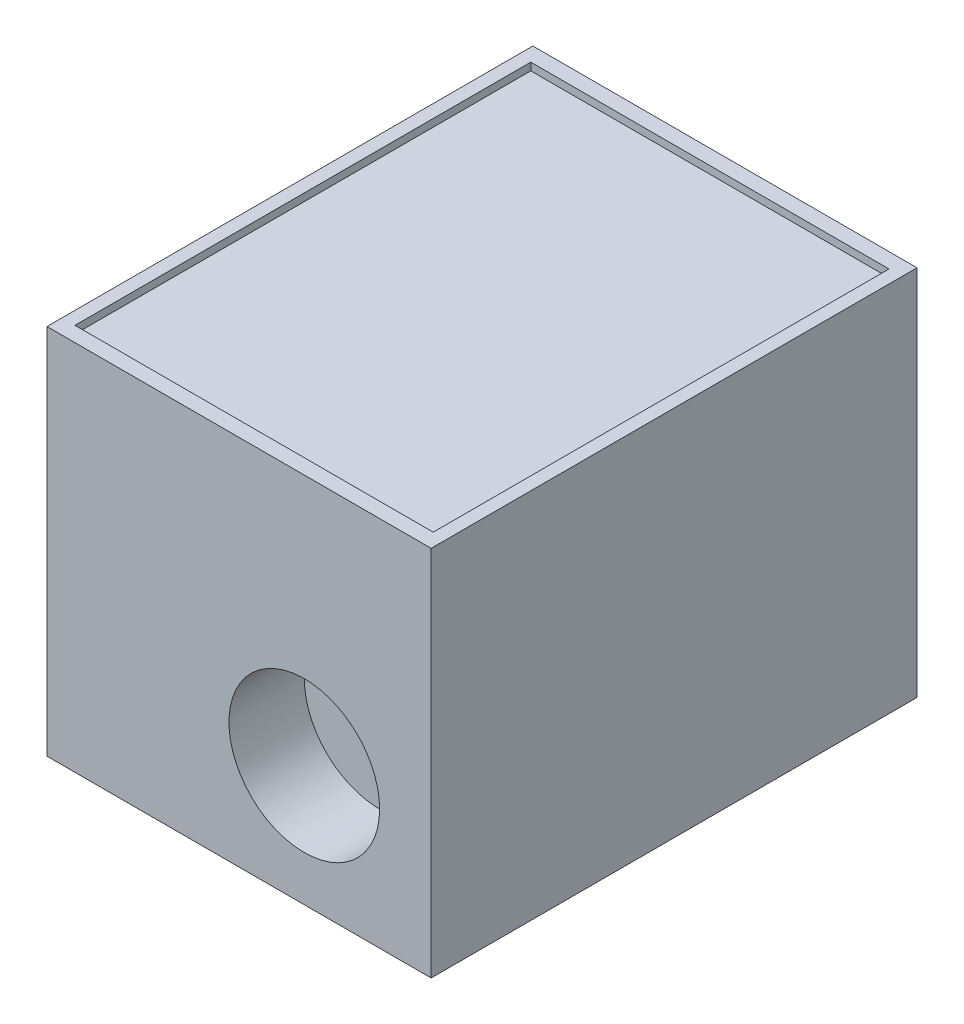
SolidWorks part; units mm, degrees
ref_plane "Front Plane" through (0, 0, 0) normal (0, 0, 1) x (1, 0, 0)
ref_plane "Top Plane" through (0, 0, 0) normal (0, 1, 0) x (1, 0, 0)
ref_plane "Right Plane" through (0, 0, 0) normal (1, 0, 0) x (0, 0, -1)
sketch "Sketch1" plane through (0, 0, 0) normal (0, 1, 0) x (1, 0, 0)
  line L1 (25.5, -32.25) -> (-25.5, -32.25)
  line L2 (25.5, -32.25) -> (25.5, 32.25)
  line L3 (25.5, 32.25) -> (-25.5, 32.25)
  line L4 (-25.5, -32.25) -> (-25.5, 32.25)
  line L5 (25.5, -32.25) -> (-25.5, 32.25) construction
  line L6 (25.5, 32.25) -> (-25.5, -32.25) construction
  point P0 (0, 0)
  dimension "D1" = 51
  dimension "D2" = 64.5
extrude "Boss-Extrude1" add sketch "Sketch1" along normal blind 49.4
sketch "Sketch2" plane through (0, 0, 32.25) normal (0, 0, 1) x (1, 0, 0)
  line L0 (25.5, 49.4) -> (25.5, 0) construction
  line L1 (-25.5, 0) -> (25.5, 0) construction
  circle A0 centre (8.66, 16) radius 10
  dimension "D1" = 16.84
  dimension "D2" = 16
  dimension "D3" = 20
extrude "Cut-Extrude1" cut sketch "Sketch2" against normal blind 10
ref_axis "Axis1" through (8.66, 16, 22.25) along (0, 0, 1)
sketch "Sketch3" plane through (0, 49.4, 0) normal (0, 1, 0) x (1, 0, 0)
  line L1 (23.7782, -30.2548) -> (-23.7782, -30.2548)
  line L2 (23.7782, -30.2548) -> (23.7782, 30.2548)
  line L3 (23.7782, 30.2548) -> (-23.7782, 30.2548)
  line L4 (-23.7782, -30.2548) -> (-23.7782, 30.2548)
  line L5 (23.7782, -30.2548) -> (-23.7782, 30.2548) construction
  line L6 (23.7782, 30.2548) -> (-23.7782, -30.2548) construction
  point P0 (0, 0)
extrude "Cut-Extrude2" cut sketch "Sketch3" against normal blind 1
